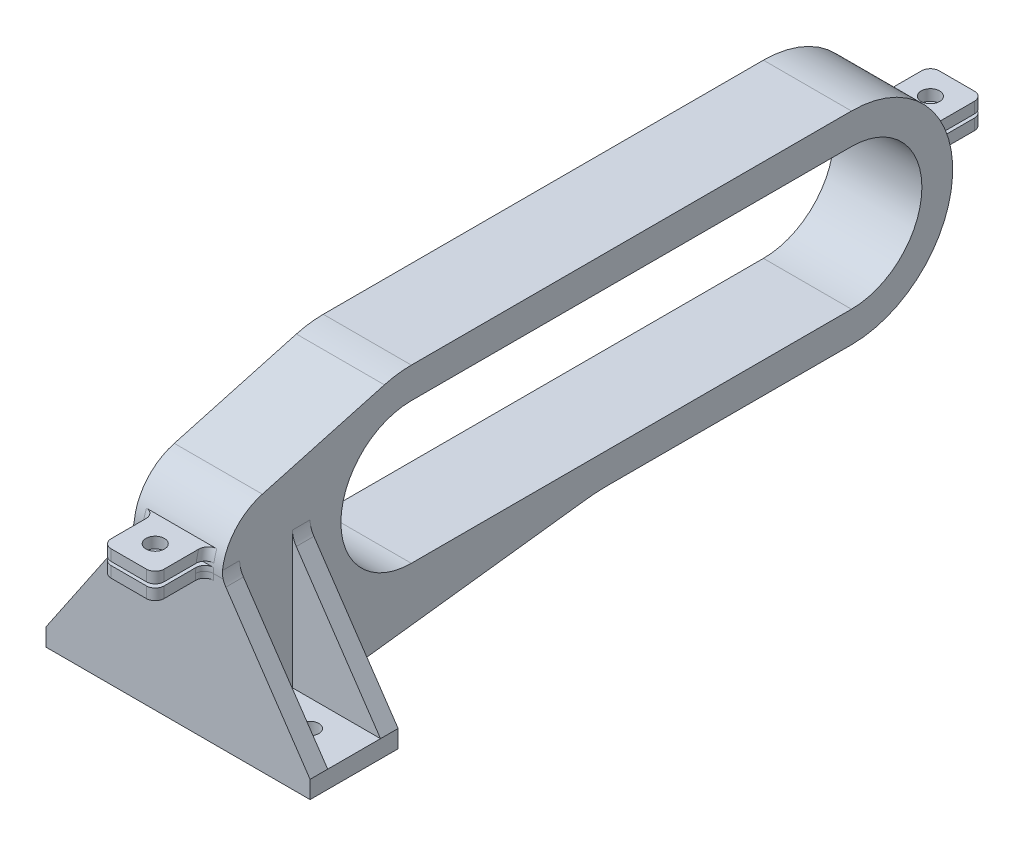
SolidWorks part; units mm, degrees
ref_plane "Front Plane" through (0, 0, 0) normal (0, 0, 1) x (1, 0, 0)
ref_plane "Top Plane" through (0, 0, 0) normal (0, 1, 0) x (1, 0, 0)
ref_plane "Right Plane" through (0, 0, 0) normal (1, 0, 0) x (0, 0, -1)
sketch "Sketch1" plane through (0, 0, 0) normal (0, 1, 0) x (1, 0, 0)
  line L0 (38.1, 0) -> (38.1, 25.4) construction
  line L1 (0, 0) -> (76.2, 0)
  line L2 (0, 0) -> (0, 25.4)
  line L3 (0, 25.4) -> (76.2, 25.4)
  line L4 (76.2, 0) -> (76.2, 25.4)
  line L5 (12.7, 12.7) -> (63.5, 12.7) construction
  circle A0 centre (12.7, 12.7) radius 2.54
  circle A1 centre (63.5, 12.7) radius 2.54
  circle A2 centre (38.1, 12.7) radius 2.54
  point P10 (38.1, 12.7)
  dimension "D2" = 5.08
  dimension "D1" = 25.4
  dimension "D3" = 50.8
  dimension "D4" = 12.7
extrude "Boss-Extrude1" add sketch "Sketch1" along normal blind 5.08
sketch "Sketch2" plane through (76.2, 0, 0) normal (1, 0, 0) x (0, 0, -1)
  line L0 (54.61, 39.37) -> (181.61, 39.37) construction
  line L1 (54.61, 59.69) -> (181.61, 59.69)
  line L2 (54.61, 19.05) -> (181.61, 19.05)
  line L3 (54.61, 68.58) -> (181.61, 68.58)
  line L4 (54.61, 10.16) -> (181.61, 10.16)
  line L5 (25.4, 5.08) -> (25.4, 0) construction
  line L6 (25.4, 0) -> (108.1466, 10.16)
  line L7 (0, 5.08) -> (0, 42.5599)
  line L8 (0, 0) -> (25.4, 0) construction
  line L9 (25.4, 0) -> (25.4, 5.08)
  line L10 (25.4, 5.08) -> (0, 5.08)
  line L11 (0, 5.08) -> (25.4, 5.08) construction
  line L12 (11.6242, 57.8215) -> (46.8486, 67.53)
  arc A0 (54.61, 59.69) -> (54.61, 19.05) centre (54.61, 39.37) ccw
  arc A1 (181.61, 19.05) -> (181.61, 59.69) centre (181.61, 39.37) ccw
  arc A2 (181.61, 10.16) -> (181.61, 68.58) centre (181.61, 39.37) ccw
  arc A3 (54.61, 68.58) -> (54.61, 10.16) centre (54.61, 39.37) ccw
  arc A4 (0, 42.5599) -> (11.6242, 57.8215) centre (15.8306, 42.5599) cw
  point P2 (118.11, 39.37)
  dimension "D2" = 20.32
  dimension "D1" = 127
  dimension "D4" = 10.16
  dimension "D5" = 7
  dimension "D3" = 8.89
extrude "Boss-Extrude2" add sketch "Sketch2" against normal blind 25.4 from offset 25.4 offset against normal yes
fillet "Fillet1" radius 50.8 1 edges at (38.1, 10.16, -108.1466)
sketch "Sketch3" plane through (0, 0, 0) normal (0, 0, 1) x (1, 0, 0)
  line L0 (50.8, 42.5599) -> (76.2, 5.08)
  line L1 (76.2, 5.08) -> (50.8, 5.08)
  line L2 (50.8, 5.08) -> (50.8, 42.5599)
  line L3 (25.4, 42.5599) -> (25.4, 5.08)
  line L4 (25.4, 5.08) -> (0, 5.08)
  line L5 (0, 5.08) -> (25.4, 42.5599)
extrude "Boss-Extrude3" add sketch "Sketch3" against normal blind 5.08
sketch "Sketch4" plane through (0, 0, -25.4) normal (0, 0, -1) x (-1, 0, 0)
  line L0 (-76.2, 5.08) -> (-50.8, 42.5599)
  line L1 (-50.8, 68.58) -> (-50.8, 10.16) construction
  line L2 (-50.8, 42.5599) -> (-50.8, 5.08)
  line L3 (-50.8, 5.08) -> (-76.2, 5.08)
  line L4 (-76.2, 5.08) -> (-50.8, 42.5599) construction
  line L5 (0, 5.08) -> (-25.4, 42.5599)
  line L6 (-25.4, 42.5599) -> (-25.4, 5.08)
  line L7 (-25.4, 5.08) -> (0, 5.08)
extrude "Boss-Extrude4" add sketch "Sketch4" against normal blind 5.08
fillet "Fillet2" radius 6.35 4 edges at (25.4, 42.5599, -2.54) (25.4, 42.5599, -22.86) (50.8, 42.5599, -22.86) (50.8, 42.5599, -2.54)
sketch "Sketch5" plane through (50.8, 0, 0) normal (1, 0, 0) x (0, 0, -1)
  line L0 (-14.2043, 45.0169) -> (0.1918, 45.0169)
  line L1 (-14.2043, 45.0169) -> (-14.2043, 48.1919)
  line L2 (-14.2043, 48.1919) -> (1.0357, 48.1919)
  line L3 (5.08, 44.5089) -> (50005.08, 44.5089) construction
  line L4 (-14.2043, 40.8259) -> (0, 40.8259)
  line L5 (-14.2043, 40.8259) -> (-14.2043, 44.0009)
  line L7 (0, 42.5599) -> (0, 40.9465) construction
  line L8 (-14.2043, 44.0009) -> (0.0657, 44.0009)
  line L9 (0, 42.5599) -> (0, 40.8259)
  line L17 (209.456, 48.1919) -> (224.696, 48.1919)
  line L18 (224.696, 48.1919) -> (224.696, 45.0169)
  line L19 (224.696, 45.0169) -> (210.269, 45.0169)
  line L20 (210.4506, 44.0009) -> (224.696, 44.0009)
  line L21 (224.696, 44.0009) -> (224.696, 40.8259)
  line L22 (224.696, 40.8259) -> (210.7837, 40.8259)
  arc A0 (11.6242, 57.8215) -> (0.1204, 44.5089) centre (15.8306, 42.5599) ccw construction
  arc A1 (1.0357, 48.1919) -> (0.1918, 45.0169) centre (15.8306, 42.5599) ccw
  arc A3 (0.1204, 44.5089) -> (0, 42.5599) centre (15.8306, 42.5599) ccw construction
  arc A4 (0.0657, 44.0009) -> (0, 42.5599) centre (15.8306, 42.5599) ccw
  arc A7 (181.61, 10.16) -> (181.61, 68.58) centre (181.61, 39.37) ccw construction
  arc A8 (210.7837, 40.8259) -> (210.4506, 44.0009) centre (181.61, 39.37) ccw
  arc A9 (210.269, 45.0169) -> (209.456, 48.1919) centre (181.61, 39.37) ccw
  dimension "D6" = 0.508
  dimension "D1" = 0.508
  dimension "D2" = 3.175
  dimension "D3" = 15.24
  dimension "D4" = 0.508
  dimension "D5" = 15.24
  dimension "D7" = 0.508
extrude "Boss-Extrude5" add sketch "Sketch5" against normal blind 15.24 from offset 5.08 offset against normal yes
sketch "Sketch6" plane through (0, 48.1919, 0) normal (0, 1, 0) x (1, 0, 0)
  line L0 (30.48, -14.2043) -> (45.72, -14.2043) construction
  line L1 (30.48, 1.0357) -> (30.48, -14.2043) construction
  line L2 (30.48, 224.696) -> (45.72, 224.696) construction
  line L5 (30.48, 224.696) -> (30.48, 209.456) construction
  circle A0 centre (38.1, -6.5843) radius 2.667
  circle A1 centre (38.1, 217.076) radius 2.667
  point P5 (38.1, -14.2043)
  point P8 (30.48, -6.5843)
  point P12 (38.1, 224.696)
  point P16 (30.48, 217.076)
  dimension "D1" = 5.334
extrude "Cut-Extrude1" cut sketch "Sketch6" against normal blind 12.7
ref_plane "Plane1" through (0, 44.5089, 0) normal (0, 1, 0) x (1, 0, 0)
fillet "Fillet3" radius 2.54 18 edges at (30.48, 41.6929, 0) (45.72, 41.6929, 0) (30.48, 42.4134, -224.696) (30.48, 42.418, -210.6605) (45.72, 42.418, -210.6605) (45.72, 42.4134, -224.696) (30.48, 46.6044, -224.696) (30.48, 46.6158, -209.907) (45.72, 46.6158, -209.907) (45.72, 46.6044, -224.696) (30.48, 42.4134, 14.2043) (30.48, 43.2812, -0.0164) (45.72, 43.2812, -0.0164) (45.72, 42.4134, 14.2043) (30.48, 46.6044, 14.2043) (30.48, 46.6264, -0.5312) (45.72, 46.6264, -0.5312) (45.72, 46.6044, 14.2043)
sketch "Sketch7" plane through (0, 44.5089, 0) normal (0, 1, 0) x (1, 0, 0)
  line L1 (162.2308, -213.5804) -> (-106.2725, -213.5804)
  line L2 (162.2308, -213.5804) -> (162.2308, 320.3142)
  line L3 (162.2308, 320.3142) -> (-106.2725, 320.3142)
  line L4 (-106.2725, -213.5804) -> (-106.2725, 320.3142)
extrude "Cut-Extrude3" [suppressed] cut sketch "Sketch7" against normal blind 230.632 contours L2 L1 L4 L3
